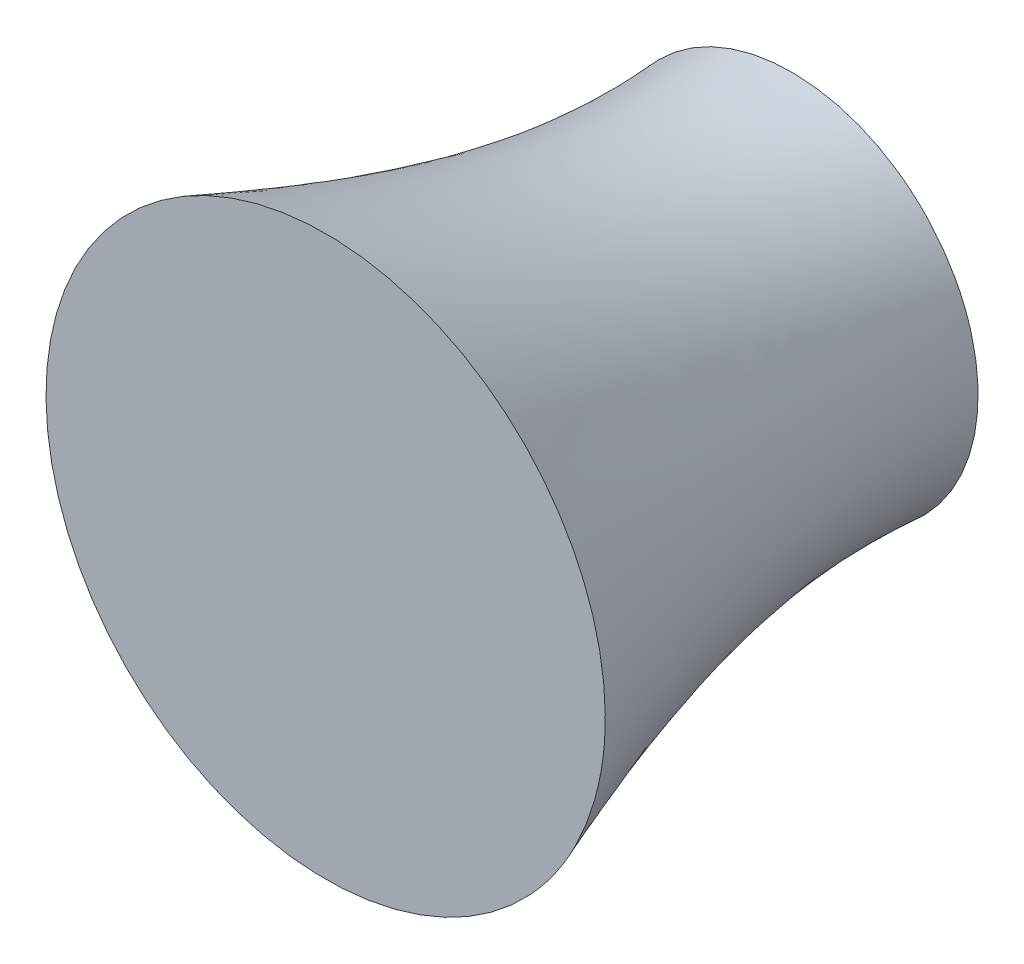
SolidWorks part; units mm, degrees
ref_plane "Front Plane" through (0, 0, 0) normal (0, 0, 1) x (1, 0, 0)
ref_plane "Top Plane" through (0, 0, 0) normal (0, 1, 0) x (1, 0, 0)
ref_plane "Right Plane" through (0, 0, 0) normal (1, 0, 0) x (0, 0, -1)
sketch "Sketch1" plane through (0, 0, 0) normal (0, 0, 1) x (1, 0, 0)
  circle A0 centre (0, 0) radius 20
  point P3 (0, 0)
  point P4 (0, 0)
ref_plane "Plane2" through (0, 0, 50) normal (0, 0, 1) x (1, 0, 0)
sketch "Sketch2" plane through (0, 0, 50) normal (0, 0, 1) x (1, 0, 0)
  circle A0 centre (0, 0) radius 30
loft "Loft2" add profiles "Sketch2", "Sketch1" connector at (-27.9758, 10.8331, 50) connector at (-16.2685, -11.6334, 0)
